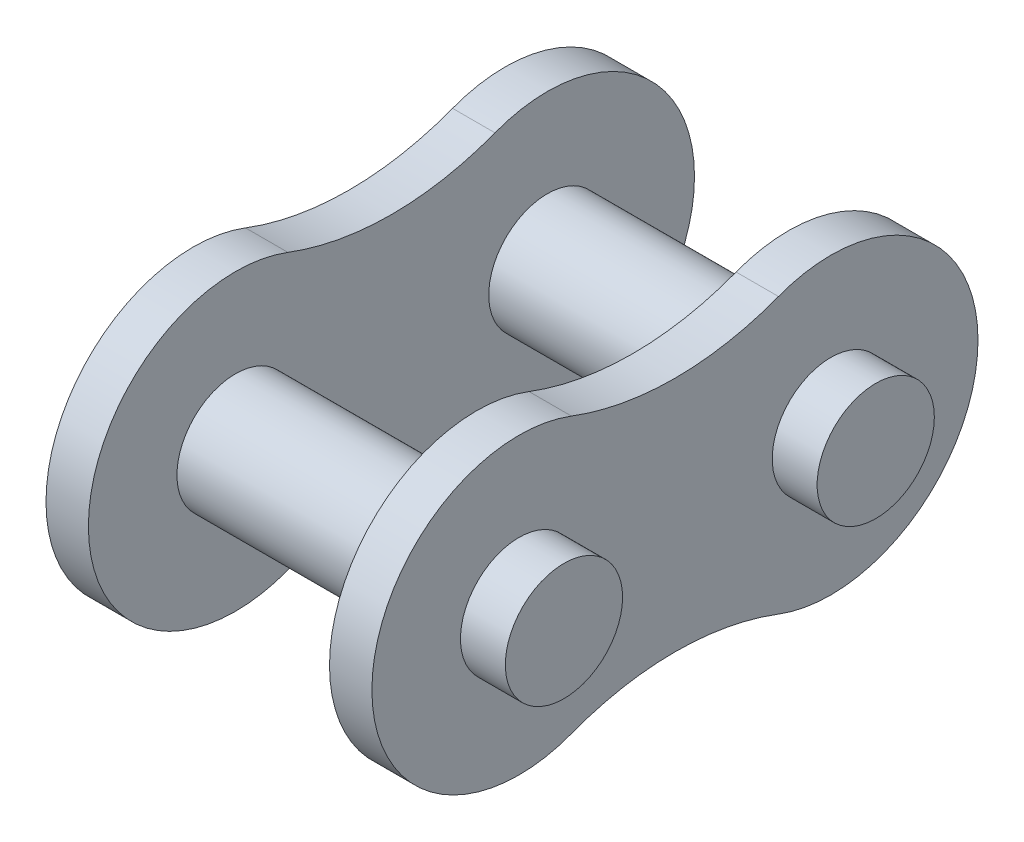
SolidWorks part; units mm, degrees
material "Plain Carbon Steel"
ref_plane "Front" through (0, 0, 0) normal (0, 0, 1) x (1, 0, 0)
ref_plane "Top" through (0, 0, 0) normal (0, 1, 0) x (1, 0, 0)
ref_plane "Right" through (0, 0, 0) normal (1, 0, 0) x (0, 0, -1)
sketch "Sketch1" plane through (0, 0, 0) normal (1, 0, 0) x (0, 0, -1)
  line L0 (0, 0) -> (9.525, 0) construction
  arc A0 (1.5995, 4.2016) -> (1.5995, -4.2016) centre (0, 0) ccw
  arc A1 (7.9255, -4.2016) -> (7.9255, 4.2016) centre (9.525, 0) ccw
  arc A2 (1.5995, 4.2016) -> (7.9255, 4.2016) centre (4.7625, 12.5099) ccw
  arc A3 (1.5995, -4.2016) -> (7.9255, -4.2016) centre (4.7625, -12.5099) cw
  circle A4 centre (0, 0) radius 2.54
  circle A5 centre (9.525, 0) radius 2.54
  circle A6 centre (9.525, 0) radius 1.7907
  circle A7 centre (0, 0) radius 1.7907
  dimension "D1" = 8.9916
  dimension "D2" = 9.525
  dimension "D3" = 8.89
  dimension "D4" = 5.08
  dimension "D5" = 3.5814
extrude "Boss-Extrude1" add sketch "Sketch1" along normal mid plane 12.7 contours A6 | A7 region at (0, 0, -9.525) region at (0, 0, 0)
extrude "Boss-Extrude2" add sketch "Sketch1<4>" along normal blind 1.2954 from offset 3.683 separate body contours A0 A3 A1 A2 A4 A5 | A7 A4 | A5 A6 | A0 A3 A1 A2 region at (0, 0, -4.7625) region at (0, 0, 2.4682) region at (0, 0, -7.0568)
sketch "Sketch1<4>" plane through (0, 0, 0) normal (1, 0, 0) x (0, 0, -1) same geometry as "Sketch1"
extrude "Boss-Extrude3" add sketch "Sketch1<5>" against normal blind 1.2954 from offset 3.683 separate body contours A0 A3 A1 A2 A4 A5 | A5 A6 | A7 A4 region at (0, 0, -4.7625) region at (0, 0, 2.4682) region at (0, 0, -7.0568) offset against normal yes
sketch "Sketch1<5>" plane through (0, 0, 0) normal (1, 0, 0) x (0, 0, -1) same geometry as "Sketch1"
